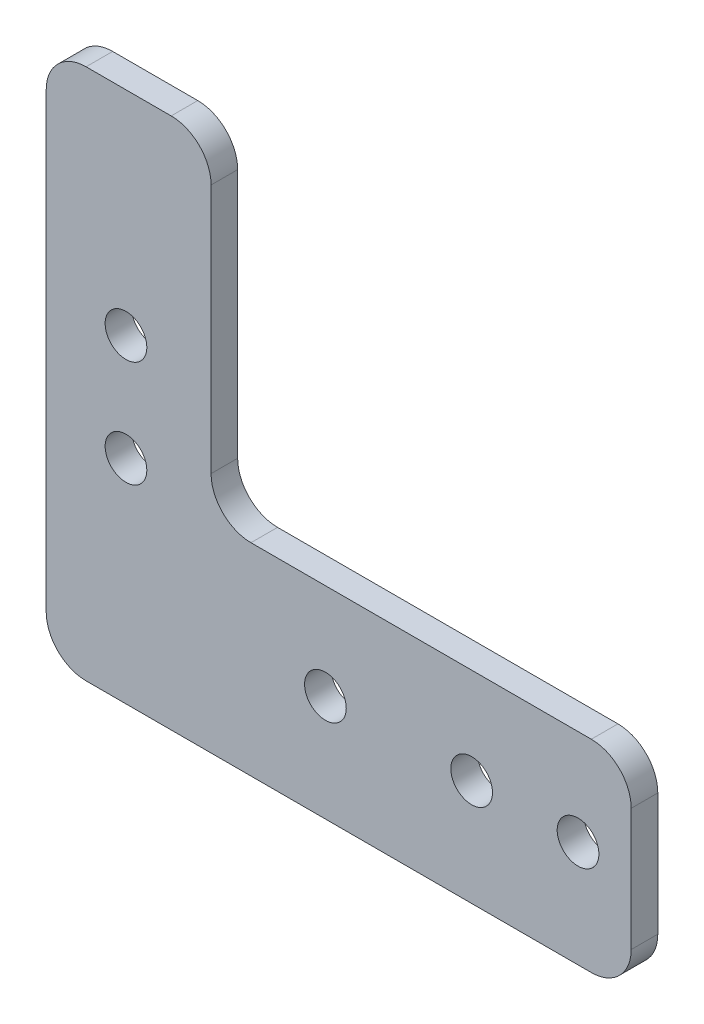
SolidWorks part; units mm, degrees
material "6061-T6 (SS)"
ref_plane "Front Plane" through (0, 0, 0) normal (0, 0, 1) x (1, 0, 0)
ref_plane "Top Plane" through (0, 0, 0) normal (0, 1, 0) x (1, 0, 0)
ref_plane "Right Plane" through (0, 0, 0) normal (1, 0, 0) x (0, 0, -1)
sketch "Sketch1" plane through (0, 0, 0) normal (0, 0, 1) x (1, 0, 0)
  line L0 (-15.24, 31.75) -> (-34.925, 31.75)
  line L1 (-34.925, -31.75) -> (34.925, -31.75) construction
  line L2 (-34.925, -31.75) -> (-34.925, 31.75)
  line L3 (-34.925, 31.75) -> (34.925, 31.75) construction
  line L4 (34.925, -31.75) -> (34.925, 31.75) construction
  line L5 (-34.925, -31.75) -> (34.925, 31.75) construction
  line L6 (-34.925, 31.75) -> (34.925, -31.75) construction
  line L7 (34.925, 31.75) -> (-15.24, 31.75) construction
  line L8 (34.925, 31.75) -> (34.925, -7.62) construction
  line L9 (34.925, -7.62) -> (-15.24, -7.62)
  line L10 (-15.24, 31.75) -> (-15.24, -7.62)
  line L19 (-25.4, 31.75) -> (-25.4, -31.75) construction
  line L20 (34.925, -7.62) -> (34.925, -31.75)
  line L24 (-34.925, -31.75) -> (34.925, -31.75)
  circle A0 centre (-25.4, -19.05) radius 2.4892
  circle A1 centre (-25.4, -6.35) radius 2.4892
  circle A2 centre (-25.4, 6.35) radius 2.4892
  circle A4 centre (-1.5875, -19.05) radius 2.4892
  circle A5 centre (15.875, -19.05) radius 2.4892
  circle A6 centre (28.575, -19.05) radius 2.4892
  point P0 (0, 0)
  dimension "D7" = 4.9784
  dimension "D6" = 33.3375
  dimension "D1" = 69.85
  dimension "D2" = 63.5
  dimension "D3" = 24.13
  dimension "D4" = 19.685
  dimension "D5" = 9.525
  dimension "D8" = 50.8
  dimension "D9" = 12.7
  dimension "D10" = 12.7
  dimension "D11" = 12.7
  dimension "D13" = 12.7
base flange "Base-Flange1" sketch "Sketch1" thickness 3.175 reverse thickness direction no parameters "D1"=0.762
fillet "Fillet2" radius 4.7625 6 edges at (34.925, -31.75, -1.5875) (34.925, -7.62, -1.5875) (-15.24, -7.62, -1.5875) (-34.925, 31.75, -1.5875) (-34.925, -31.75, -1.5875) (-15.24, 31.75, -1.5875)
sketch "Bend-Lines1" [suppressed] plane through (0, 0, 0) normal (0, 1, 0) x (1, 0, 0)
sketch "Bounding-Box1" [suppressed] plane through (0, 0, 0) normal (0, 1, 0) x (1, 0, 0)
sheet metal parameters "Sheet-Metal3" thickness 3.175 parameters "D1"=0.762
flat pattern "Flat-Pattern3" [suppressed]
sketch "Bend-Lines2" plane through (0, 0, 0) normal (0, 1, 0) x (1, 0, 0)
sketch3d "Bounding-Box2" [suppressed]
  line L0 (-34.925, 31.75, 0) -> (34.925, 31.75, 0) construction
  line L1 (-34.925, -31.75, 0) -> (34.925, -31.75, 0) construction
  line L2 (-34.925, 31.75, 0) -> (-34.925, -31.75, 0) construction
  line L3 (34.925, 31.75, 0) -> (34.925, -31.75, 0) construction
